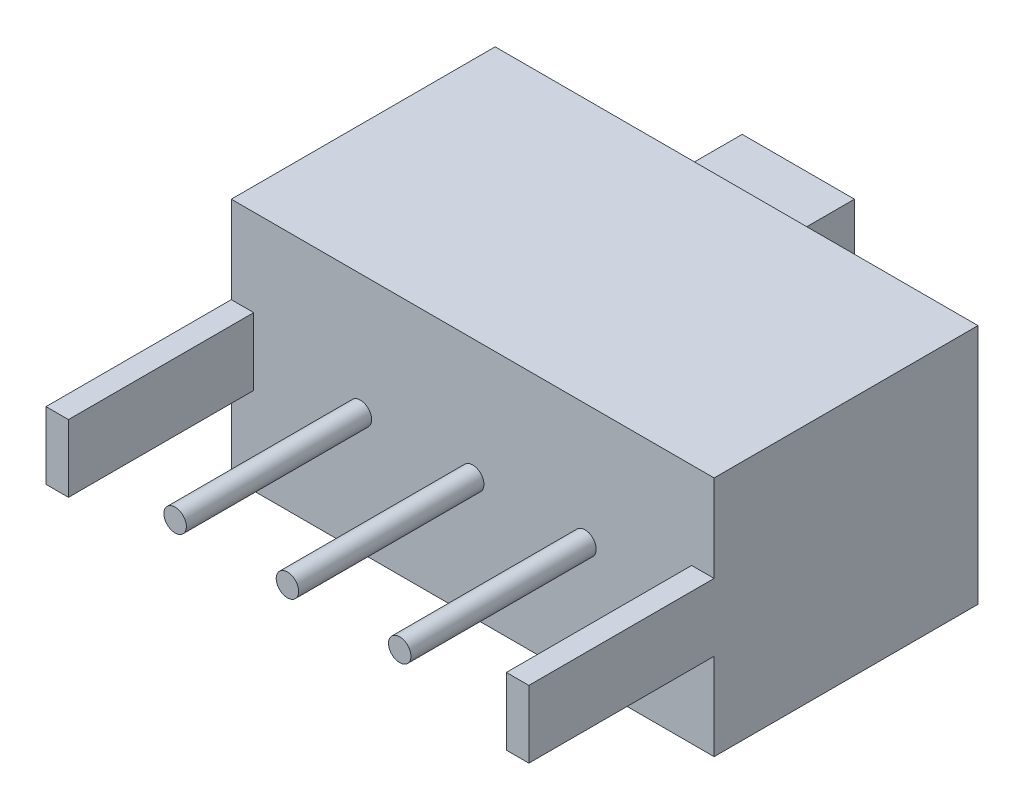
SolidWorks part; units mm, degrees
ref_plane "前视基准面" through (0, 0, 0) normal (0, 0, 1) x (1, 0, 0)
ref_plane "上视基准面" through (0, 0, 0) normal (0, 1, 0) x (1, 0, 0)
ref_plane "右视基准面" through (0, 0, 0) normal (1, 0, 0) x (0, 0, -1)
other "Configuration Table"
sketch "草图1" plane through (0, 0, 0) normal (0, 0, 1) x (1, 0, 0)
  line L1 (0, 0) -> (8.6, 0)
  line L2 (0, 0) -> (0, -4.3)
  line L3 (0, -4.3) -> (8.6, -4.3)
  line L4 (8.6, 0) -> (8.6, -4.3)
  line L5 (2.3, -1.05) -> (6.3, -1.05)
  line L6 (2.3, -1.05) -> (2.3, -3.25)
  line L7 (2.3, -3.25) -> (6.3, -3.25)
  line L8 (6.3, -1.05) -> (6.3, -3.25)
  line L9 (2.4, -1.15) -> (4.4, -1.15)
  line L10 (2.4, -1.15) -> (2.4, -3.15)
  line L11 (2.4, -3.15) -> (4.4, -3.15)
  line L12 (4.4, -1.15) -> (4.4, -3.15)
  point P13 (4.3, -4.3)
  point P14 (4.3, -3.25)
  point P15 (2.3, -2.15)
  point P16 (0, -2.15)
  dimension "D1" = 8.6
  dimension "D2" = 4.3
  dimension "D3" = 4
  dimension "D4" = 2.2
  dimension "D5" = 2
  dimension "D6" = 0.1
  dimension "D7" = 2
  dimension "D8" = 2.4
extrude "凸台-拉伸1" add sketch "草图1" along normal blind 4.7 contours L2 L3 L4 L1
extrude "切除-拉伸1" cut sketch "草图1<3>" along normal blind 0.2 contours L5 L8 L7 L6 | L12 L11 L10 L9
sketch "草图1<3>" plane through (0, 0, 0) normal (0, 0, 1) x (1, 0, 0) same geometry as "草图1"
extrude "凸台-拉伸2" add sketch "草图1<4>" against normal blind 2 contours L12 L11 L10 L9
sketch "草图1<4>" plane through (0, 0, 0) normal (0, 0, 1) x (1, 0, 0) same geometry as "草图1"
sketch "草图2" plane through (0, 0, 4.7) normal (0, 0, 1) x (1, 0, 0)
  line L5 (8.6, 0) -> (8.6, -4.3) construction
  line L6 (8.6, -1.55) -> (8.2, -1.55)
  line L7 (8.6, -1.55) -> (8.6, -2.75)
  line L8 (8.6, -2.75) -> (8.2, -2.75)
  line L9 (8.2, -1.55) -> (8.2, -2.75)
  line L11 (0, -1.55) -> (0.4, -1.55)
  line L12 (0, -1.55) -> (0, -2.75)
  line L13 (0, -2.75) -> (0.4, -2.75)
  line L14 (0.4, -1.55) -> (0.4, -2.75)
  line L15 (0, 0) -> (8.6, -4.3)
  line L17 (0, 0) -> (0, -4.3) construction
  circle A0 centre (2.3, -2.15) radius 0.2
  circle A1 centre (4.3, -2.15) radius 0.2
  circle A2 centre (6.3, -2.15) radius 0.2
  point P4 (0, -2.15)
  point P5 (8.2, -2.15)
  dimension "D3" = 0.4
  dimension "D4" = 0.4
  dimension "D1" = 2
  dimension "D2" = 2
  dimension "D5" = 1.2
extrude "凸台-拉伸3" add sketch "草图2" along normal blind 3.3 contours L13 L14 L11 L12 | A0 | A1 | A2 | L8 L9 L6 L7
